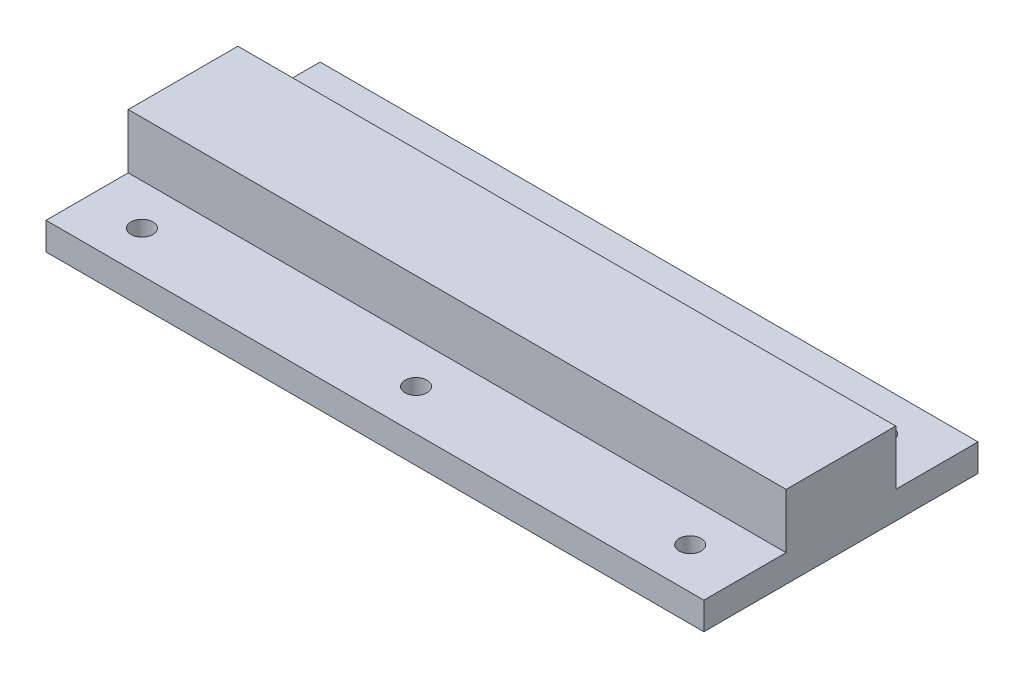
SolidWorks part; units mm, degrees
ref_plane "Front Plane" through (0, 0, 0) normal (0, 0, 1) x (1, 0, 0)
ref_plane "Top Plane" through (0, 0, 0) normal (0, 1, 0) x (1, 0, 0)
ref_plane "Right Plane" through (0, 0, 0) normal (1, 0, 0) x (0, 0, -1)
sketch "Sketch2" plane through (0, 0, 0) normal (0, 1, 0) x (1, 0, 0)
  line L0 (-46.8981, 34.5466) -> (-46.8981, -15.4534)
  line L1 (-46.8981, -15.4534) -> (73.1019, -15.4534)
  line L2 (73.1019, -15.4534) -> (73.1019, 34.5466)
  line L3 (73.1019, 34.5466) -> (-46.8981, 34.5466)
  dimension "D1" = 120
  dimension "D2" = 50
extrude "Boss-Extrude1" add sketch "Sketch2" along normal blind 15
sketch "Sketch3" plane through (0, 0, 0) normal (0, 1, 0) x (1, 0, 0)
  line L0 (74.3548, 9.5466) -> (-56.2815, 9.5466) construction
  line L1 (63.1019, 9.5466) -> (63.1019, 17.0466)
  line L2 (63.1019, 17.0466) -> (3.1019, 17.0466)
  line L3 (3.1019, 17.0466) -> (3.1019, 19.5466)
  line L4 (3.1019, 19.5466) -> (-36.8981, 19.5466)
  line L5 (-36.8981, 19.5466) -> (-36.8981, 9.5466)
  line L6 (-36.8981, 9.5466) -> (63.1019, 9.5466)
  line L7 (73.1019, -15.4534) -> (73.1019, 34.5466) construction
  line L9 (-46.8981, -15.4534) -> (73.1019, -15.4534) construction
  dimension "D1" = 60
  dimension "D2" = 40
  dimension "D3" = 10
  dimension "D4" = 25
  dimension "D5" = 10
  dimension "D6" = 7.5
sketch "Skizze7" plane through (-46.8981, 0, 0) normal (-1, 0, 0) x (0, 0, 1)
  line L1 (-34.5466, 0) -> (15.4534, 0) construction
  line L3 (-9.5466, -6.0172) -> (-9.5466, 6.0172) construction
  line L4 (15.4534, 15) -> (15.4534, 0) construction
  line L5 (-34.5466, 15) -> (-34.5466, 0) construction
  circle A0 centre (-9.5466, 2.5) radius 1.5
  dimension "D1" = 3
  dimension "D2" = 2.5
extrude "Schnitt-Linear austragen6" cut sketch "Skizze7" against normal blind 10
revolve "Schnitt-Rotation1" cut sketch "Sketch3" angle 360 about L0
sketch "Skizze10" plane through (0, 0, 0) normal (0, -1, 0) x (1, 0, 0)
  line L0 (63.1019, -17.0466) -> (3.1019, -17.0466) construction
  line L1 (53.1019, -17.0466) -> (40.6019, -17.0466)
  line L2 (53.1019, -17.0466) -> (53.1019, -14.5466)
  line L3 (53.1019, -14.5466) -> (40.6019, -14.5466)
  line L4 (40.6019, -17.0466) -> (40.6019, -14.5466)
  line L5 (63.1019, -2.0466) -> (63.1019, -17.0466) construction
  line L10 (85.7448, -9.5466) -> (-66.8579, -9.5466) construction
  line L11 (-46.8981, 15.4534) -> (73.1019, 15.4534) construction
  line L12 (73.1019, -34.5466) -> (-46.8981, -34.5466) construction
  dimension "D1" = 10
  dimension "D2" = 12.5
  dimension "D5" = 2.5
revolve "Rotation3" add sketch "Skizze10" angle 180 about L10 reverse direction yes
sketch "Skizze11" plane through (0, 0, 0) normal (0, -1, 0) x (1, 0, 0)
  line L0 (40.6019, -17.0466) -> (3.1019, -17.0466) construction
  line L1 (28.1019, -17.0466) -> (15.6019, -17.0466)
  line L2 (28.1019, -17.0466) -> (28.1019, -14.5466)
  line L3 (28.1019, -14.5466) -> (15.6019, -14.5466)
  line L4 (15.6019, -17.0466) -> (15.6019, -14.5466)
  line L5 (53.1019, -14.5466) -> (40.6019, -14.5466) construction
  line L6 (40.6019, -14.5466) -> (40.6019, -17.0466) construction
  line L7 (95.0378, -9.5466) -> (-94.5432, -9.5466) construction
  line L8 (-46.8981, 15.4534) -> (73.1019, 15.4534) construction
  line L9 (73.1019, -34.5466) -> (-46.8981, -34.5466) construction
  point P10 (40.6019, -15.7966)
  dimension "D1" = 12.5
  dimension "D2" = 12.5
revolve "Rotation4" add sketch "Skizze11" angle 180 about L7 reverse direction yes
sketch "Skizze12" plane through (0, 0, 0) normal (0, -1, 0) x (1, 0, 0)
  line L0 (73.1019, 15.4534) -> (73.1019, -34.5466) construction
  line L1 (-46.8981, -34.5466) -> (-46.8981, 15.4534) construction
  line L3 (-46.8981, 15.4534) -> (73.1019, 15.4534) construction
  circle A0 centre (-36.8981, 7.9534) radius 2
  circle A1 centre (13.1019, 7.9534) radius 2
  circle A2 centre (63.1019, 7.9534) radius 2
  dimension "D3" = 4
  dimension "D2" = 10
  dimension "D4" = 10
  dimension "D5" = 7.5
  dimension "D1" = 3
ref_plane "Ebene6" through (0, 0, -9.5466) normal (0, 0, 1) x (1, 0, 0)
extrude "Schnitt-Linear austragen7" cut sketch "Skizze12" against normal through all
mirror "Spiegeln1" about plane through (0, 0, -9.5466) normal (0, 0, 1) of "Schnitt-Linear austragen7"
sketch "Skizze13" plane through (-46.8981, 0, 0) normal (-1, 0, 0) x (0, 0, 1)
  line L0 (-34.5466, 0) -> (15.4534, 0) construction
  line L1 (15.4534, 15) -> (0.4534, 15)
  line L2 (15.4534, 15) -> (15.4534, 5)
  line L3 (15.4534, 5) -> (0.4534, 5)
  line L4 (0.4534, 15) -> (0.4534, 5)
  line L5 (-34.5466, 0) -> (15.4534, 0) construction
  line L6 (-34.5466, 15) -> (-19.5466, 15)
  line L7 (-34.5466, 15) -> (-34.5466, 5)
  line L8 (-34.5466, 5) -> (-19.5466, 5)
  line L9 (-19.5466, 15) -> (-19.5466, 5)
  dimension "D1" = 15
  dimension "D2" = 5
  dimension "D3" = 15
  dimension "D4" = 5
extrude "Schnitt-Linear austragen8" cut sketch "Skizze13" against normal through all contours L2 L1 L4 L3 | L7 L6 L9 L8
